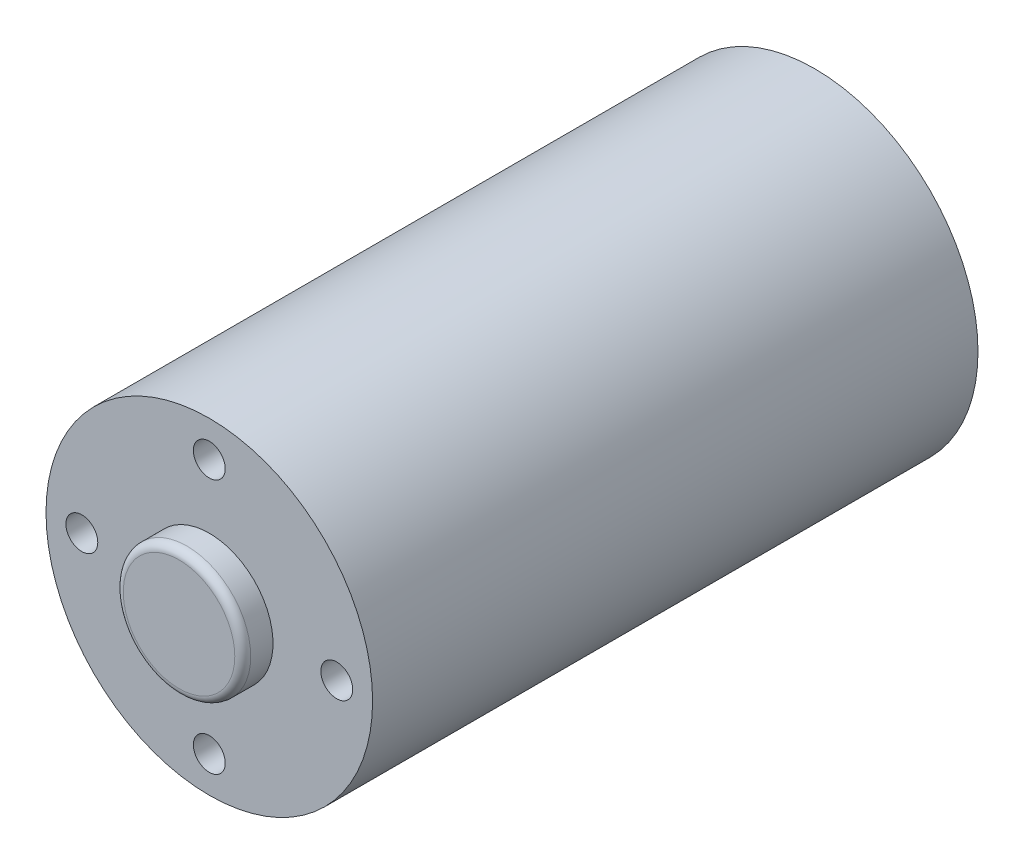
SolidWorks part; units mm, degrees
ref_plane "Front Plane" through (0, 0, 0) normal (0, 0, 1) x (1, 0, 0)
ref_plane "Top Plane" through (0, 0, 0) normal (0, 1, 0) x (1, 0, 0)
ref_plane "Right Plane" through (0, 0, 0) normal (1, 0, 0) x (0, 0, -1)
sketch "Sketch1" plane through (0, 0, 0) normal (0, 0, 1) x (1, 0, 0)
  circle A0 centre (0, 0) radius 10.25
  dimension "D1" = 20.5
extrude "Boss-Extrude1" add sketch "Sketch1" along normal blind 19 and the other way blind 19
sketch "Sketch2" plane through (0, 0, 19) normal (0, 0, 1) x (1, 0, 0)
  circle A0 centre (0, 0) radius 4
extrude "Boss-Extrude2" add sketch "Sketch2" along normal blind 1.9
sketch "Sketch3" plane through (0, 0, -19) normal (0, 0, -1) x (-1, 0, 0)
  circle A0 centre (0, 0) radius 4
  dimension "D1" = 8
extrude "Boss-Extrude3" add sketch "Sketch3" along normal blind 1
sketch "Sketch4" plane through (0, 0, 19) normal (0, 0, 1) x (1, 0, 0)
  circle A0 centre (0, 0) radius 8
  circle A1 centre (0, 8) radius 1
  circle A2 centre (8, 0) radius 1
  circle A3 centre (0, -8) radius 1
  circle A4 centre (-8, 0) radius 1
  point P14 (0, 0)
  dimension "D1" = 4
extrude "Cut-Extrude1" cut sketch "Sketch4" against normal blind 3.5 contours A0 A1 | A0 A4 | A0 A3 | A0 A2 | A0 A2 | A0 A3 | A0 A4 | A1 region at (7.5645, 0, 19) region at (8.413, 0, 19) region at (0, 7.5645, 19) region at (0, -8.413, 19) region at (0, -7.5645, 19) region at (-7.5645, 0, 19) region at (-8.413, 0, 19)
fillet "Fillet1" radius 0.5 1 edges at (4, 0, 20.9)
ref_plane "Plane1" through (0, 0, 0) normal (0, 0, -1) x (-1, 0, 0)
mirror "Mirror1" about plane through (0, 0, 0) normal (0, 0, -1) of "Cut-Extrude1"
